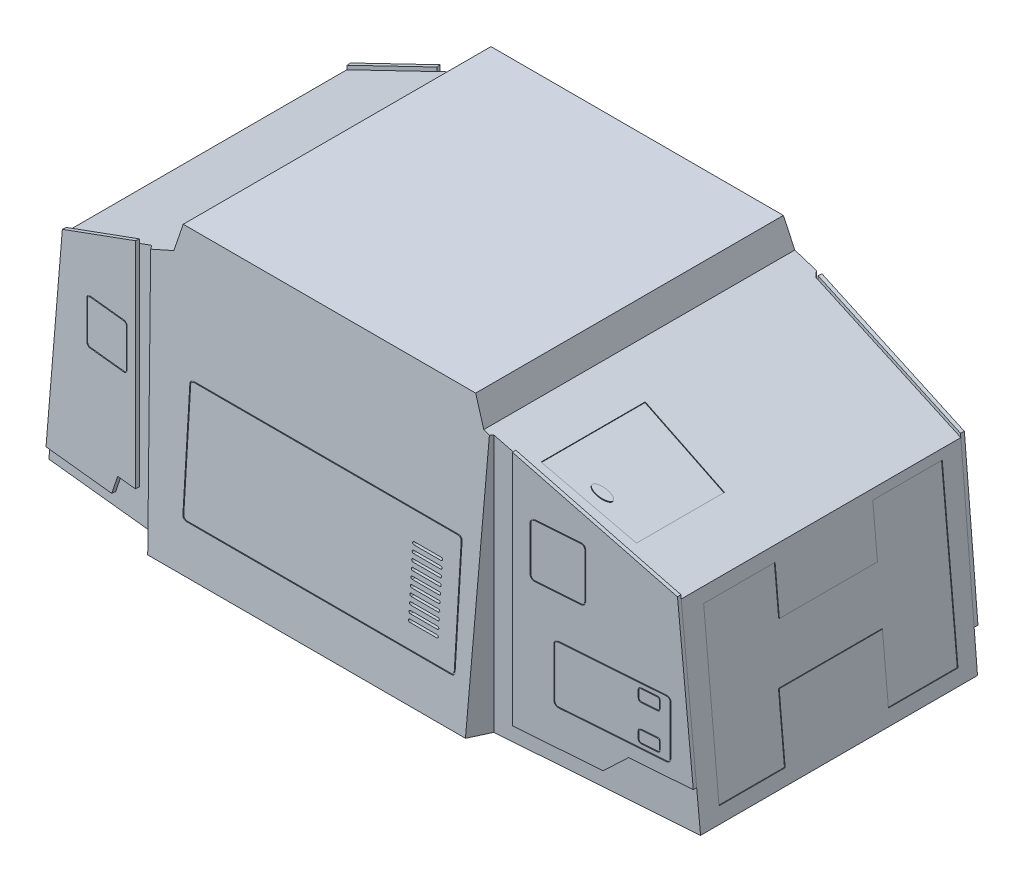
SolidWorks part; units mm, degrees
ref_plane "Front Plane" through (0, 0, 0) normal (0, 0, 1) x (1, 0, 0)
ref_plane "Top Plane" through (0, 0, 0) normal (0, 1, 0) x (1, 0, 0)
ref_plane "Right Plane" through (0, 0, 0) normal (1, 0, 0) x (0, 0, -1)
sketch "Sketch3" plane through (0, 0, 0) normal (0, 1, 0) x (1, 0, 0)
  line L1 (-180, 95) -> (180, 95)
  line L2 (-180, 95) -> (-180, -95)
  line L3 (-180, -95) -> (180, -95)
  line L4 (180, 95) -> (180, -95)
  line L5 (-180, 95) -> (180, -95) construction
  line L6 (-180, -95) -> (180, 95) construction
  point P0 (0, 0)
  dimension "D1" = 190
  dimension "D2" = 360
extrude "Boss-Extrude2" add sketch "Sketch3" along normal blind 158
sketch "Sketch4" plane through (180, 0, 0) normal (1, 0, 0) x (0, 0, -1)
  line L0 (-95, 0) -> (-95, 158)
  line L1 (-95, 158) -> (-85, 158)
  line L2 (-95, 158) -> (95, 158) construction
  line L3 (-85, 158) -> (-95, 0)
  line L4 (0, 0) -> (0, 123.75) construction
  line L5 (85, 158) -> (95, 0)
  line L6 (95, 158) -> (85, 158)
  line L7 (95, 0) -> (95, 158)
  dimension "D1" = 170
extrude "Cut-Extrude1" cut sketch "Sketch4" against normal through all
sketch "Sketch5" plane through (0, 0, 0) normal (0, 0, 1) x (1, 0, 0)
  line L0 (-180, 0) -> (-165.5, 158)
  line L1 (-180, 158) -> (180, 158) construction
  line L2 (-165.5, 158) -> (-180, 158)
  line L3 (-180, 158) -> (-180, 0)
  line L4 (0, 0) -> (0, 158) construction
  line L5 (180, 158) -> (180, 0)
  line L6 (165.5, 158) -> (180, 158)
  line L7 (180, 0) -> (165.5, 158)
  dimension "D1" = 331
extrude "Cut-Extrude2" cut sketch "Sketch5" against normal through all both and the other way through all
sketch "Sketch6" plane through (0, 0, 0) normal (0, 0, 1) x (1, 0, 0)
  line L0 (180, 0) -> (180, 105) construction
  line L2 (-165.5, 158) -> (165.5, 158) construction
  line L3 (64, 145.6686) -> (180, 105)
  line L4 (180, 105) -> (180, 158)
  line L5 (-180, 110) -> (-180, 158)
  line L6 (-180, 158) -> (-97, 158)
  line L8 (-180, 0) -> (-180, 110) construction
  line L9 (64, 145.6686) -> (64, 158)
  line L10 (64, 158) -> (180, 158)
  line L11 (-180, 110) -> (-97, 145.6686)
  line L12 (-97, 145.6686) -> (-97, 158)
  dimension "D1" = 105
  dimension "D2" = 110
  dimension "D3" = 83
  dimension "D4" = 116
extrude "Cut-Extrude3" cut sketch "Sketch6" along normal through all both and the other way through all
sketch "Sketch8" plane through (0, 0, 0) normal (0, 1, 0) x (1, 0, 0)
  line L0 (-180, 76.5) -> (-97, 85)
  line L3 (-180, 95) -> (-180, -95) construction
  line L4 (-180, 111.8161) -> (-180, 76.5)
  line L5 (0, 0) -> (-198.7212, 0) construction
  line L11 (-180, 111.8161) -> (-97, 111.8161)
  line L12 (-97, 111.8161) -> (-97, 85)
  line L13 (-97, -111.8161) -> (-97, -85)
  line L14 (-180, -111.8161) -> (-97, -111.8161)
  line L15 (-180, -111.8161) -> (-180, -76.5)
  line L16 (-180, -76.5) -> (-97, -85)
  line L17 (64, 85) -> (64, 140.1812)
  line L18 (64, 85) -> (180, 76.5)
  line L19 (180, 76.5) -> (197.104, 166.0233)
  line L20 (197.104, 166.0233) -> (64, 140.1812)
  line L21 (197.104, -166.0233) -> (64, -140.1812)
  line L22 (180, -76.5) -> (197.104, -166.0233)
  line L23 (64, -85) -> (180, -76.5)
  line L24 (64, -85) -> (64, -140.1812)
  line L29 (180, -95) -> (180, 95) construction
  dimension "D1" = 153
extrude "Cut-Extrude4" cut sketch "Sketch8" against normal through all and the other way through all
sketch "Sketch10" plane through (0, 0, 0) normal (0, -1, 0) x (1, 0, 0)
  line L1 (-156.5, -79) -> (156.5, -79) construction
  line L2 (-156.5, -79) -> (-156.5, 79) construction
  line L3 (-156.5, 79) -> (156.5, 79) construction
  line L4 (156.5, -79) -> (156.5, 79) construction
  line L5 (-156.5, -79) -> (156.5, 79) construction
  line L6 (-156.5, 79) -> (156.5, -79) construction
  point P0 (0, 0)
  dimension "D1" = 313
  dimension "D2" = 158
shell "Shell6" thickness 5 removed face at (-11, 0, 0)
sketch "Sketch11" plane through (0, 0, 0) normal (0, -1, 0) x (1, 0, 0)
  line L0 (-97, 95) -> (64, 95) construction
  line L1 (-97, 95) -> (64, 95)
  line L14 (-97, 95) -> (-97, 85)
  line L15 (-97, 85) -> (-180, 76.5)
  line L16 (-180, 76.5) -> (-180, -76.5)
  line L17 (-180, -76.5) -> (-97, -85)
  line L18 (-97, -85) -> (-97, -95)
  line L19 (-97, -95) -> (64, -95)
  line L20 (64, -95) -> (64, -85)
  line L21 (64, -85) -> (180, -76.5)
  line L22 (180, -76.5) -> (180, 76.5)
  line L23 (180, 76.5) -> (64, 85)
  line L24 (64, 85) -> (64, 95)
  line L25 (64, 95) -> (-97, 95)
  line L26 (-97, 95) -> (-97, 85)
  line L27 (-97, 85) -> (-180, 76.5)
  line L28 (-180, 76.5) -> (-180, -76.5)
  line L29 (-180, -76.5) -> (-97, -85)
  line L30 (-97, -85) -> (-97, -95)
  line L31 (-97, -95) -> (64, -95)
  line L32 (64, -95) -> (64, -85)
  line L33 (64, -85) -> (180, -76.5)
  line L34 (180, -76.5) -> (180, 76.5)
  line L35 (180, 76.5) -> (64, 85)
  line L36 (64, 85) -> (64, 95)
  line L37 (64, 95) -> (-97, 95)
  line M25 (-92, 80.4859) -> (-92, 89.99)
  line M26 (-92, 89.99) -> (59, 89.99)
  line M27 (59, 89.99) -> (59, 80.353)
  line M28 (59, 80.353) -> (174.979, 71.8545)
  line M29 (174.979, 71.8545) -> (174.979, -71.8545)
  line M30 (174.979, -71.8545) -> (59, -80.353)
  line M31 (59, -80.353) -> (59, -89.99)
  line M32 (59, -89.99) -> (-92, -89.99)
  line M33 (-92, -89.99) -> (-92, -80.4859)
  line M34 (-92, -80.4859) -> (-174.979, -71.988)
  line M35 (-174.979, -71.988) -> (-174.979, 71.988)
  line M36 (-174.979, 71.988) -> (-92, 80.4859)
  dimension "D1" = 0
extrude "Boss-Extrude3" add sketch "Sketch11" against normal blind 5 contours M25 M36 M35 M34 M33 M32 M31 M30 M29 M28 M27 M26 region at (-1.4169, 0, 0)
chamfer "Chamfer1" distance 19.9 angle 25 2 edges at (-97, 72.8343, -85) (64, 72.8343, 85) first distance on face at (-97, 75.9172, 0) first distance on face at (64, 75.9172, 0)
chamfer "Chamfer2" distance 19.9 angle 25 2 edges at (-97, 72.8343, 85) (64, 72.8343, -85) first distance on face at (-97, 101.2229, 29.8699) first distance on face at (64, 101.2229, -29.8699)
chamfer "Chamfer3" distance 10 angle 45 2 edges at (73.6078, 71.1501, -84.296) (-106.7449, 70.7404, 84.002) first distance on face at (124.3148, 62.6977, -80.5804) first distance on face at (-140.7451, 63.9993, 80.5201)
chamfer "Chamfer4" distance 5 angle 50 1 edges at (-97, 145.6686, 0) first distance on face at (-122.0326, 134.911, -0.0994)
chamfer "Chamfer5" distance 6 angle 50 1 edges at (64, 145.6686, 0) first distance on face at (97.4296, 133.9485, 0.0677)
sketch "Sketch18" plane through (-9.6212, 0, 93.9484) normal (-0.1019, 0, 0.9948) x (0.9948, 0, 0.1019)
  line L0 (-160.4966, 116.7807) -> (-170.6066, 7.1902)
  line L1 (-171.2699, 0) -> (-160.7055, 114.5163) construction
  line L2 (-170.6066, 7.1902) -> (-129.9277, 7.1902)
  line L3 (-129.9277, 7.1902) -> (-126.2803, 17.3621)
  line L4 (-126.2803, 17.3621) -> (-115.3442, 17.3621)
  line L5 (-115.3442, 17.3621) -> (-115.3442, 136.0837)
  line L7 (-115.3442, 136.0837) -> (-160.4966, 116.7807)
  line L11 (-107.6316, 0) -> (-171.2699, 0) construction
  line L12 (-107.6316, 0) -> (-107.6316, 137.2058) construction
  line L14 (-107.6316, 137.2058) -> (-160.7055, 114.5163) construction
  dimension "D1" = 2
extrude "Boss-Extrude5" add sketch "Sketch18" along normal blind 2
sketch "Sketch19" plane through (-9.825, 0, 95.938) normal (-0.1019, 0, 0.9948) x (0.9948, 0, 0.1019)
  line L0 (-144.8175, 92.3146) -> (-144.8175, 71.3428)
  line L1 (-143.3175, 94.3146) -> (-122.3457, 94.3146)
  line L2 (-145.3175, 92.3146) -> (-145.3175, 71.3428)
  line L3 (-143.3175, 69.3428) -> (-122.3457, 69.3428)
  line L4 (-120.3457, 92.3146) -> (-120.3457, 71.3428)
  line L5 (-145.3175, 94.3146) -> (-122.3457, 69.3428) construction
  line L6 (-145.3175, 69.3428) -> (-120.3457, 94.3146) construction
  line L7 (-143.3175, 69.8428) -> (-122.3457, 69.8428)
  line L8 (-120.8457, 92.3146) -> (-120.8457, 71.3428)
  line L9 (-143.3175, 93.8146) -> (-122.3457, 93.8146)
  arc A0 (-122.3457, 94.3146) -> (-120.3457, 92.3146) centre (-122.3457, 92.3146) cw
  arc A1 (-122.3457, 69.3428) -> (-120.3457, 71.3428) centre (-122.3457, 71.3428) ccw
  arc A2 (-145.3175, 71.3428) -> (-143.3175, 69.3428) centre (-143.3175, 71.3428) ccw
  arc A3 (-143.3175, 94.3146) -> (-145.3175, 92.3146) centre (-143.3175, 92.3146) ccw
  arc A4 (-144.8175, 71.3428) -> (-143.3175, 69.8428) centre (-143.3175, 71.3428) ccw
  arc A5 (-122.3457, 69.8428) -> (-120.8457, 71.3428) centre (-122.3457, 71.3428) ccw
  arc A6 (-122.3457, 93.8146) -> (-120.8457, 92.3146) centre (-122.3457, 92.3146) cw
  arc A7 (-143.3175, 93.8146) -> (-144.8175, 92.3146) centre (-143.3175, 92.3146) ccw
  point P0 (-133.3524, 81.3079)
  dimension "D1" = 2
  dimension "D2" = 0.5
extrude "Cut-Extrude5" cut sketch "Sketch19" against normal blind 0.5
sketch "Sketch20" plane through (0, 5.9887, 94.621) normal (0, 0.0632, 0.998) x (1, 0, 0)
  line L0 (-89.2026, 82.2629) -> (-89.2026, 21.0896)
  line L1 (-86.7026, 83.7629) -> (58.7101, 83.7629)
  line L2 (-88.7026, 81.7629) -> (-88.7026, 21.5896)
  line L3 (-86.7026, 19.5896) -> (58.7101, 19.5896)
  line L4 (60.7101, 81.7629) -> (60.7101, 21.5896)
  line L5 (-88.7026, 83.7629) -> (60.7101, 19.5896) construction
  line L6 (-88.7026, 19.5896) -> (60.7101, 83.7629) construction
  line L7 (-87.2026, 19.0896) -> (59.2101, 19.0896)
  line L8 (61.2101, 82.2629) -> (61.2101, 21.0896)
  line L9 (-87.2026, 84.2629) -> (59.2101, 84.2629)
  line L10 (61.2101, 84.2629) -> (61.2101, 19.0896) construction
  line L11 (-89.2026, 84.2629) -> (61.2101, 84.2629) construction
  line L12 (-88.7026, 83.7629) -> (60.7101, 83.7629) construction
  line L13 (60.7101, 83.7629) -> (60.7101, 19.5896) construction
  line L14 (-88.7026, 19.5896) -> (60.7101, 19.5896) construction
  line L15 (-89.2026, 19.0896) -> (61.2101, 19.0896) construction
  line L16 (-89.2026, 84.2629) -> (-89.2026, 19.0896) construction
  line L17 (-88.7026, 83.7629) -> (-88.7026, 19.5896) construction
  arc A0 (61.2101, 82.2629) -> (59.2101, 84.2629) centre (59.2101, 82.2629) ccw
  arc A1 (58.7101, 83.7629) -> (60.7101, 81.7629) centre (58.7101, 81.7629) cw
  arc A2 (58.7101, 19.5896) -> (60.7101, 21.5896) centre (58.7101, 21.5896) ccw
  arc A3 (59.2101, 19.0896) -> (61.2101, 21.0896) centre (59.2101, 21.0896) ccw
  arc A4 (-89.2026, 21.0896) -> (-87.2026, 19.0896) centre (-87.2026, 21.0896) ccw
  arc A5 (-88.7026, 21.5896) -> (-86.7026, 19.5896) centre (-86.7026, 21.5896) ccw
  arc A6 (-89.2026, 82.2629) -> (-87.2026, 84.2629) centre (-87.2026, 82.2629) cw
  arc A7 (-86.7026, 83.7629) -> (-88.7026, 81.7629) centre (-86.7026, 81.7629) ccw
  point P0 (-13.9963, 51.6763)
  dimension "D2" = 2
  dimension "D1" = 0.5
extrude "Cut-Extrude6" cut sketch "Sketch20" against normal blind 0.5
sketch "Sketch21" plane through (6.537, 0, 89.2107) normal (0.0731, 0, 0.9973) x (0.9973, 0, -0.0731)
  line L0 (78.6105, 140.2638) -> (78.6105, 9.5077)
  line L2 (163.945, 108.4906) -> (173.9281, 0) construction
  line L3 (171.9049, 21.987) -> (163.7609, 110.4906)
  line L4 (163.7609, 110.4906) -> (78.6105, 140.2638)
  line L6 (67.2506, 142.3002) -> (67.2506, 0) construction
  line L8 (78.6105, 9.5077) -> (125.3303, 9.5077)
  line L9 (125.3303, 9.5077) -> (138.5436, 21.987)
  line L10 (138.5436, 21.987) -> (171.9049, 21.987)
  line L11 (163.945, 108.4906) -> (67.2506, 142.3002) construction
  line L12 (163.945, 108.4906) -> (175.2328, 108.4906) construction
  dimension "D1" = 2
extrude "Boss-Extrude6" add sketch "Sketch21" along normal blind 2
sketch "Sketch22" plane through (6.6831, 0, 91.2053) normal (0.0731, 0, 0.9973) x (0.9973, 0, -0.0731)
  line L0 (99.9186, 58.3939) -> (99.9186, 31.5005)
  line L1 (90.1817, 112.8938) -> (113.9275, 112.8938)
  line L2 (88.1817, 110.8938) -> (88.1817, 86.2383)
  line L3 (90.1817, 84.2383) -> (113.9275, 84.2383)
  line L4 (115.9275, 110.8938) -> (115.9275, 86.2383)
  line L5 (88.1817, 112.8938) -> (115.9275, 84.2383) construction
  line L6 (88.1817, 84.2383) -> (115.9275, 112.8938) construction
  line L7 (102.4186, 60.3939) -> (157.9396, 60.3939)
  line L8 (100.4186, 58.3939) -> (100.4186, 31.5005)
  line L9 (102.4186, 29.5005) -> (157.9396, 29.5005)
  line L10 (159.9396, 58.3939) -> (159.9396, 31.5005)
  line L11 (100.4186, 60.3939) -> (159.9396, 29.5005) construction
  line L12 (100.4186, 29.5005) -> (159.9396, 60.3939) construction
  line L13 (144.9909, 57.8533) -> (153.382, 57.8533)
  line L14 (143.9909, 56.8533) -> (143.9909, 52.772)
  line L15 (144.9909, 51.772) -> (153.382, 51.772)
  line L16 (154.382, 56.8533) -> (154.382, 52.772)
  line L17 (143.9909, 57.8533) -> (154.382, 51.772) construction
  line L18 (143.9909, 51.772) -> (154.382, 57.8533) construction
  line L19 (144.9909, 38.1224) -> (153.382, 38.1224)
  line L20 (143.9909, 37.1224) -> (143.9909, 33.0411)
  line L21 (144.9909, 32.0411) -> (153.382, 32.0411)
  line L22 (154.382, 37.1224) -> (154.382, 33.0411)
  line L23 (143.9909, 38.1224) -> (154.382, 32.0411) construction
  line L24 (143.9909, 32.0411) -> (154.382, 38.1224) construction
  line L25 (102.4186, 29.0005) -> (157.9396, 29.0005)
  line L26 (160.4396, 58.3939) -> (160.4396, 31.5005)
  line L27 (102.4186, 60.8939) -> (157.9396, 60.8939)
  line L28 (87.6817, 110.8938) -> (87.6817, 86.2383)
  line L29 (90.1817, 83.7383) -> (113.9275, 83.7383)
  line L30 (116.4275, 110.8938) -> (116.4275, 86.2383)
  line L31 (90.1817, 113.3938) -> (113.9275, 113.3938)
  line L32 (143.4909, 56.8533) -> (143.4909, 52.772)
  line L33 (144.9909, 51.272) -> (153.382, 51.272)
  line L34 (154.882, 56.8533) -> (154.882, 52.772)
  line L35 (144.9909, 58.3533) -> (153.382, 58.3533)
  line L36 (143.4909, 37.1224) -> (143.4909, 33.0411)
  line L37 (144.9909, 31.5411) -> (153.382, 31.5411)
  line L38 (154.882, 37.1224) -> (154.882, 33.0411)
  line L39 (144.9909, 38.6224) -> (153.382, 38.6224)
  arc A0 (157.9396, 60.3939) -> (159.9396, 58.3939) centre (157.9396, 58.3939) cw
  arc A1 (157.9396, 29.5005) -> (159.9396, 31.5005) centre (157.9396, 31.5005) ccw
  arc A2 (100.4186, 31.5005) -> (102.4186, 29.5005) centre (102.4186, 31.5005) ccw
  arc A3 (102.4186, 60.3939) -> (100.4186, 58.3939) centre (102.4186, 58.3939) ccw
  arc A4 (113.9275, 112.8938) -> (115.9275, 110.8938) centre (113.9275, 110.8938) cw
  arc A5 (113.9275, 84.2383) -> (115.9275, 86.2383) centre (113.9275, 86.2383) ccw
  arc A6 (88.1817, 86.2383) -> (90.1817, 84.2383) centre (90.1817, 86.2383) ccw
  arc A7 (90.1817, 112.8938) -> (88.1817, 110.8938) centre (90.1817, 110.8938) ccw
  arc A8 (143.9909, 33.0411) -> (144.9909, 32.0411) centre (144.9909, 33.0411) ccw
  arc A9 (153.382, 38.1224) -> (154.382, 37.1224) centre (153.382, 37.1224) cw
  arc A10 (153.382, 32.0411) -> (154.382, 33.0411) centre (153.382, 33.0411) ccw
  arc A11 (144.9909, 38.1224) -> (143.9909, 37.1224) centre (144.9909, 37.1224) ccw
  arc A12 (143.9909, 52.772) -> (144.9909, 51.772) centre (144.9909, 52.772) ccw
  arc A13 (153.382, 51.772) -> (154.382, 52.772) centre (153.382, 52.772) ccw
  arc A14 (153.382, 57.8533) -> (154.382, 56.8533) centre (153.382, 56.8533) cw
  arc A15 (144.9909, 57.8533) -> (143.9909, 56.8533) centre (144.9909, 56.8533) ccw
  arc A16 (99.9186, 31.5005) -> (102.4186, 29.0005) centre (102.4186, 31.5005) ccw
  arc A17 (157.9396, 29.0005) -> (160.4396, 31.5005) centre (157.9396, 31.5005) ccw
  arc A18 (157.9396, 60.8939) -> (160.4396, 58.3939) centre (157.9396, 58.3939) cw
  arc A19 (102.4186, 60.8939) -> (99.9186, 58.3939) centre (102.4186, 58.3939) ccw
  arc A20 (87.6817, 86.2383) -> (90.1817, 83.7383) centre (90.1817, 86.2383) ccw
  arc A21 (113.9275, 83.7383) -> (116.4275, 86.2383) centre (113.9275, 86.2383) ccw
  arc A22 (113.9275, 113.3938) -> (116.4275, 110.8938) centre (113.9275, 110.8938) cw
  arc A23 (90.1817, 113.3938) -> (87.6817, 110.8938) centre (90.1817, 110.8938) ccw
  arc A24 (143.4909, 52.772) -> (144.9909, 51.272) centre (144.9909, 52.772) ccw
  arc A25 (153.382, 51.272) -> (154.882, 52.772) centre (153.382, 52.772) ccw
  arc A26 (153.382, 58.3533) -> (154.882, 56.8533) centre (153.382, 56.8533) cw
  arc A27 (144.9909, 58.3533) -> (143.4909, 56.8533) centre (144.9909, 56.8533) ccw
  arc A28 (143.4909, 33.0411) -> (144.9909, 31.5411) centre (144.9909, 33.0411) ccw
  arc A29 (153.382, 31.5411) -> (154.882, 33.0411) centre (153.382, 33.0411) ccw
  arc A30 (153.382, 38.6224) -> (154.882, 37.1224) centre (153.382, 37.1224) cw
  arc A31 (144.9909, 38.6224) -> (143.4909, 37.1224) centre (144.9909, 37.1224) ccw
  point P0 (102.0546, 98.566)
  point P5 (130.1791, 44.9472)
  point P10 (149.1865, 35.0818)
  point P11 (149.1865, 54.8126)
  dimension "D1" = 2
  dimension "D2" = 1
  dimension "D3" = 0.5
  dimension "D4" = 0.5
  dimension "D5" = 0.5
  dimension "D6" = 0.5
extrude "Cut-Extrude7" cut sketch "Sketch22" against normal blind 0.5 contours L31 A23 L28 A20 L29 A21 L30 A22 A7 L1 A4 L4 A5 L3 A6 L2 | L27 A19 L0 A16 L25 A17 L26 A18 A3 L7 A0 L10 A1 L9 A2 L8 | L35 A27 L32 A24 L33 A25 L34 A26 A15 L13 A14 L16 A13 L15 A12 L14 | L39 A31 L36 A28 L37 A29 L38 A30 A11 L19 A9 L22 A10 L21 A8 L20 region at (107.1131, 60.1133, 83.8462) region at (95.152, 112.3695, 84.7227) region at (150.3231, 57.8191, 80.68) region at (150.3231, 38.0882, 80.68)
sketch "Sketch23" plane through (0, 5.9887, 94.621) normal (0, 0.0632, 0.998) x (1, 0, 0)
  line L0 (35.4779, 68.5836) -> (50.4779, 68.5836) construction
  line L1 (35.4779, 69.3336) -> (50.4779, 69.3336)
  line L2 (35.4779, 67.8336) -> (50.4779, 67.8336)
  line L3 (42.9779, 68.5836) -> (42.9779, 41.1335) construction
  line L4 (35.4779, 64.5836) -> (50.4779, 64.5836) construction
  line L5 (35.4779, 65.3336) -> (50.4779, 65.3336)
  line L6 (35.4779, 63.8336) -> (50.4779, 63.8336)
  line L7 (35.4779, 60.5836) -> (50.4779, 60.5836) construction
  line L8 (35.4779, 61.3336) -> (50.4779, 61.3336)
  line L9 (35.4779, 59.8336) -> (50.4779, 59.8336)
  line L10 (35.4779, 56.5836) -> (50.4779, 56.5836) construction
  line L11 (35.4779, 57.3336) -> (50.4779, 57.3336)
  line L12 (35.4779, 55.8336) -> (50.4779, 55.8336)
  line L13 (35.4779, 52.5836) -> (50.4779, 52.5836) construction
  line L14 (35.4779, 53.3336) -> (50.4779, 53.3336)
  line L15 (35.4779, 51.8336) -> (50.4779, 51.8336)
  line L16 (35.4779, 48.5836) -> (50.4779, 48.5836) construction
  line L17 (35.4779, 49.3336) -> (50.4779, 49.3336)
  line L18 (35.4779, 47.8336) -> (50.4779, 47.8336)
  line L19 (35.4779, 44.5836) -> (50.4779, 44.5836) construction
  line L20 (35.4779, 45.3336) -> (50.4779, 45.3336)
  line L21 (35.4779, 43.8336) -> (50.4779, 43.8336)
  line L22 (35.4779, 40.5836) -> (50.4779, 40.5836) construction
  line L23 (35.4779, 41.3336) -> (50.4779, 41.3336)
  line L24 (35.4779, 39.8336) -> (50.4779, 39.8336)
  line L25 (35.4779, 36.5836) -> (50.4779, 36.5836) construction
  line L26 (35.4779, 37.3336) -> (50.4779, 37.3336)
  line L27 (35.4779, 35.8336) -> (50.4779, 35.8336)
  line L28 (35.4779, 32.5836) -> (50.4779, 32.5836) construction
  line L29 (35.4779, 33.3336) -> (50.4779, 33.3336)
  line L30 (35.4779, 31.8336) -> (50.4779, 31.8336)
  arc A0 (35.4779, 69.3336) -> (35.4779, 67.8336) centre (35.4779, 68.5836) ccw
  arc A1 (50.4779, 67.8336) -> (50.4779, 69.3336) centre (50.4779, 68.5836) ccw
  arc A2 (35.4779, 65.3336) -> (35.4779, 63.8336) centre (35.4779, 64.5836) ccw
  arc A3 (50.4779, 63.8336) -> (50.4779, 65.3336) centre (50.4779, 64.5836) ccw
  arc A4 (35.4779, 61.3336) -> (35.4779, 59.8336) centre (35.4779, 60.5836) ccw
  arc A5 (50.4779, 59.8336) -> (50.4779, 61.3336) centre (50.4779, 60.5836) ccw
  arc A6 (35.4779, 57.3336) -> (35.4779, 55.8336) centre (35.4779, 56.5836) ccw
  arc A7 (50.4779, 55.8336) -> (50.4779, 57.3336) centre (50.4779, 56.5836) ccw
  arc A8 (35.4779, 53.3336) -> (35.4779, 51.8336) centre (35.4779, 52.5836) ccw
  arc A9 (50.4779, 51.8336) -> (50.4779, 53.3336) centre (50.4779, 52.5836) ccw
  arc A10 (35.4779, 49.3336) -> (35.4779, 47.8336) centre (35.4779, 48.5836) ccw
  arc A11 (50.4779, 47.8336) -> (50.4779, 49.3336) centre (50.4779, 48.5836) ccw
  arc A12 (35.4779, 45.3336) -> (35.4779, 43.8336) centre (35.4779, 44.5836) ccw
  arc A13 (50.4779, 43.8336) -> (50.4779, 45.3336) centre (50.4779, 44.5836) ccw
  arc A14 (35.4779, 41.3336) -> (35.4779, 39.8336) centre (35.4779, 40.5836) ccw
  arc A15 (50.4779, 39.8336) -> (50.4779, 41.3336) centre (50.4779, 40.5836) ccw
  arc A16 (35.4779, 37.3336) -> (35.4779, 35.8336) centre (35.4779, 36.5836) ccw
  arc A17 (50.4779, 35.8336) -> (50.4779, 37.3336) centre (50.4779, 36.5836) ccw
  arc A18 (35.4779, 33.3336) -> (35.4779, 31.8336) centre (35.4779, 32.5836) ccw
  arc A19 (50.4779, 31.8336) -> (50.4779, 33.3336) centre (50.4779, 32.5836) ccw
  point P2 (42.9779, 68.5836)
  point P13 (42.9779, 64.5836)
  point P20 (42.9779, 60.5836)
  point P27 (42.9779, 56.5836)
  point P34 (42.9779, 52.5836)
  point P41 (42.9779, 48.5836)
  point P48 (42.9779, 44.5836)
  point P55 (42.9779, 40.5836)
  point P62 (42.9779, 36.5836)
  point P69 (42.9779, 32.5836)
  dimension "D1" = 1.5
  dimension "D2" = 15
  dimension "D4" = 4
  dimension "D3" = 10
extrude "Cut-Extrude8" cut sketch "Sketch23" against normal up to next
sketch "Sketch24" plane through (-132.805, 39.9565, 0) normal (-0.9576, 0.2881, 0) x (0, 0, 1)
  line L0 (0, 0) -> (0, 138.6299) construction
  line L1 (-70.0038, 121.648) -> (-70.0038, 110.9297)
  line L2 (-74.0038, 121.648) -> (-22.0038, 121.648)
  line L3 (-74.0038, 121.648) -> (-74.0038, 110.9297)
  line L4 (-74.0038, 110.9297) -> (-22.0038, 110.9297)
  line L5 (-22.0038, 121.648) -> (-22.0038, 110.9297)
  line L6 (-74.0038, 121.648) -> (-22.0038, 110.9297) construction
  line L7 (-74.0038, 110.9297) -> (-22.0038, 121.648) construction
  line L8 (-66.0038, 121.648) -> (-66.0038, 110.9297)
  line L9 (-62.0038, 121.648) -> (-62.0038, 110.9297)
  line L10 (-58.0038, 121.648) -> (-58.0038, 110.9297)
  line L11 (-54.0038, 121.648) -> (-54.0038, 110.9297)
  line L12 (-50.0038, 121.648) -> (-50.0038, 110.9297)
  line L13 (-46.0038, 121.648) -> (-46.0038, 110.9297)
  line L14 (-42.0038, 121.648) -> (-42.0038, 110.9297)
  line L15 (-38.0038, 121.648) -> (-38.0038, 110.9297)
  line L16 (-34.0038, 121.648) -> (-34.0038, 110.9297)
  line L17 (-30.0038, 121.648) -> (-30.0038, 110.9297)
  line L18 (-26.0038, 121.648) -> (-26.0038, 110.9297)
  line L19 (-22.0038, 121.648) -> (-22.0038, 110.9297)
  point P3 (-48.0038, 116.2888)
  dimension "D2" = 52
  dimension "D3" = 4
  dimension "D4" = 4
  dimension "D1" = 13
extrude "Cut-Extrude9" cut sketch "Sketch24" against normal up to next contours L3 L4 L1 L2 | L9 L2 L8 L4 | L11 L2 L10 L4 | L13 L2 L12 L4 | L15 L2 L14 L4 | L17 L2 L16 L4 | L2 L18 L4 L5
mirror "Mirror1" about plane through (0, 0, 0) normal (0, 0, 1) of "Cut-Extrude9", "Cut-Extrude7", "Cut-Extrude6", "Cut-Extrude5", "Boss-Extrude5", "Boss-Extrude6", "Cut-Extrude8"
sketch "Sketch25" plane through (-178.4967, 16.381, 0) normal (-0.9958, 0.0914, 0) x (0, 0, 1)
  line L12 (-73.5279, -13.4499) -> (73.5279, -13.4499)
  line L13 (73.5677, -9.2014) -> (74.5481, 95.5477)
  line L14 (74.5481, 95.5477) -> (-74.5481, 95.5477)
  line L15 (-74.5481, 95.5477) -> (-73.5677, -9.2014)
  line L16 (-73.5279, -13.4499) -> (73.5279, -13.4499)
  line L17 (73.5677, -9.2014) -> (74.5481, 95.5477)
  line L18 (74.5481, 95.5477) -> (-74.5481, 95.5477)
  line L19 (-74.5481, 95.5477) -> (-73.5677, -9.2014)
  line L20 (73.5279, -13.4499) -> (73.5677, -9.2014)
  line L21 (73.5279, -13.4499) -> (73.5677, -9.2014)
  line L22 (-73.5677, -9.2014) -> (-73.5279, -13.4499)
  line L23 (-73.5677, -9.2014) -> (-73.5279, -13.4499)
  dimension "D1" = 3
extrude "Cut-Extrude10" cut sketch "Sketch25" against normal blind 1
sketch "Sketch26" plane through (52.4855, 149.7055, 0) normal (0.3308, 0.9437, 0) x (0.9437, -0.3308, 0)
  line L0 (93.9118, -72.9864) -> (93.9118, -24.3785)
  line L5 (93.9118, -24.3785) -> (42.7728, -19.9044)
  line L6 (42.7728, -19.9044) -> (42.7728, -77.4604)
  line L8 (42.7728, -77.4604) -> (93.9118, -72.9864)
  ellipse E0 centre (67.5901, -66.9324) end of major axis (62.2316, -67.5868) minor radius 2.6176
  dimension "D1" = 95
extrude "Cut-Extrude11" cut sketch "Sketch26" against normal blind 0.5 contours L6 L8 L0 L5 E0 region at (116.3016, 127.3321, 48.379)
sketch "Sketch29" plane through (178.4967, 16.381, 0) normal (0.9958, 0.0914, 0) x (0, 0, -1)
  line L0 (-65.5393, 84.8137) -> (-65.5393, -8.1386)
  line L1 (-65.5393, -8.1386) -> (-28.9885, -8.1386)
  line L2 (-28.9885, -8.1386) -> (-28.9885, 28.097)
  line L3 (-28.9885, 28.097) -> (28.0432, 28.097)
  line L4 (28.0432, 28.097) -> (28.0432, -8.1386)
  line L5 (28.0432, -8.1386) -> (66.4845, -8.1386)
  line L6 (66.4845, -8.1386) -> (66.4845, 87.3345)
  line L7 (66.4845, 87.3345) -> (28.1238, 87.3345)
  line L8 (28.1238, 87.3345) -> (28.1238, 58.9761)
  line L9 (28.1238, 58.9761) -> (-26.0721, 58.9761)
  line L10 (-26.0721, 58.9761) -> (-26.0721, 84.8137)
  line L11 (-26.0721, 84.8137) -> (-65.5393, 84.8137)
extrude "Cut-Extrude12" cut sketch "Sketch29" against normal blind 0.4
sketch "Sketch31" plane through (0, 0, 0) normal (0, 0, 1) x (1, 0, 0)
  line L1 (0, 0) -> (215.7861, 0)
  line L2 (0, 0) -> (0, 167.887)
  line L3 (0, 167.887) -> (215.7861, 167.887)
  line L4 (215.7861, 0) -> (215.7861, 167.887)
sketch "Sketch32" plane through (0, 0, 0) normal (0, 0, 1) x (1, 0, 0)
  line L1 (0, 0) -> (-188.9502, 0)
  line L2 (0, 0) -> (0, 184.6213)
  line L3 (0, 184.6213) -> (-188.9502, 184.6213)
  line L4 (-188.9502, 0) -> (-188.9502, 184.6213)
